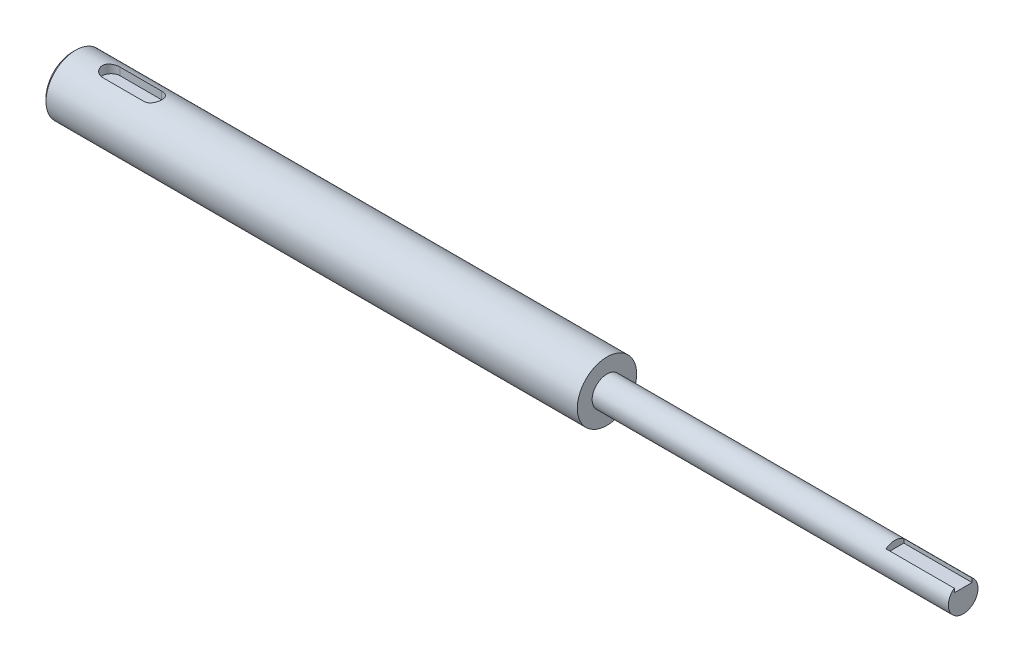
SolidWorks part; units mm, degrees
material "45"
ref_plane "前视基准面" through (0, 0, 0) normal (0, 0, 1) x (1, 0, 0)
ref_plane "上视基准面" through (0, 0, 0) normal (0, 1, 0) x (1, 0, 0)
ref_plane "右视基准面" through (0, 0, 0) normal (1, 0, 0) x (0, 0, -1)
ref_axis "基准轴1" through (88.99, 0, 0) along (-1, 0, 0)
sketch "草图1" plane through (0, 0, 0) normal (1, 0, 0) x (0, 0, -1)
  circle A0 centre (0, 0) radius 10
extrude "凸台-拉伸1" add sketch "草图1" along normal blind 150
ref_plane "基准面1" through (0, 10, 0) normal (0, 1, 0) x (1, 0, 0)
sketch "草图2" plane through (0, 10, 0) normal (0, 1, 0) x (1, 0, 0)
  line L0 (13, 3) -> (27, 3)
  line L1 (13, -3) -> (27, -3)
  arc A0 (13, 3) -> (13, -3) centre (13, 0) ccw
  arc A1 (27, 3) -> (27, -3) centre (27, 0) cw
  dimension "D1" = 3
  dimension "D2" = 14
extrude "切除-拉伸1" cut sketch "草图2" against normal blind 3
chamfer "倒角1" distance 1 angle 45 1 edges at (0, 0, -10)
sketch "草图3" plane through (150, 0, 0) normal (1, 0, 0) x (0, 0, -1)
  circle A0 centre (0, 0) radius 10
extrude "凸台-拉伸2" add sketch "草图3" along normal blind 150
ref_plane "基准面2" through (0, 10, 0) normal (0, 1, 0) x (1, 0, 0)
sketch "草图4" plane through (0, 10, 0) normal (0, 1, 0) x (1, 0, 0)
  line L0 (273, 3) -> (287, 3)
  line L1 (273, -3) -> (287, -3)
  arc A0 (273, 3) -> (273, -3) centre (273, 0) ccw
  arc A1 (287, 3) -> (287, -3) centre (287, 0) cw
  dimension "D1" = 3
  dimension "D2" = 14
extrude "切除-拉伸2" cut sketch "草图4" against normal blind 3
chamfer "倒角2" distance 1 angle 45 1 edges at (300, 0, -10)
sketch "草图5" plane through (300, 0, 0) normal (1, 0, 0) x (0, 0, -1)
  circle A0 centre (0, 0) radius 10
  circle A1 centre (0, 0) radius 5
  dimension "D1" = 10
extrude "切除-拉伸3" cut sketch "草图5" against normal blind 120
sketch "草图6" plane through (300, 0, 0) normal (1, 0, 0) x (0, 0, -1)
  line L6 (3, 2.6704) -> (3, 6.7485)
  line L7 (3, 6.7485) -> (-3, 6.7485)
  line L8 (-3, 2.6704) -> (-3, 6.7485)
  line L9 (-1.1871, 2.6704) -> (-3, 6.7485) construction
  line L10 (3, 6.7485) -> (1.1871, 2.6704) construction
  line L11 (-3, 2.6704) -> (3, 2.6704)
  point P0 (0, 0)
  dimension "D1" = 6
extrude "切除-拉伸4" cut sketch "草图6" against normal blind 23
